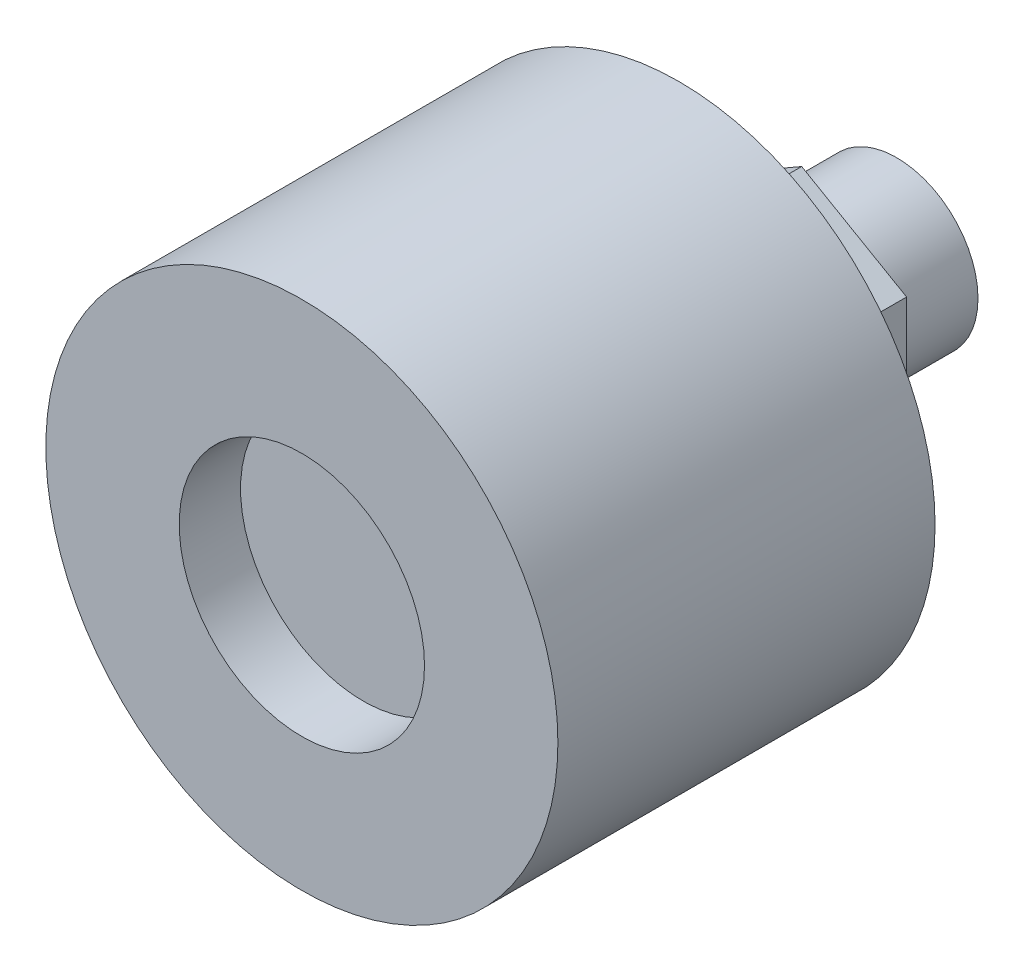
SolidWorks part; units mm, degrees
material "1060 Alloy"
ref_plane "Front Plane" through (0, 0, 0) normal (0, 0, 1) x (1, 0, 0)
ref_plane "Top Plane" through (0, 0, 0) normal (0, 1, 0) x (1, 0, 0)
ref_plane "Right Plane" through (0, 0, 0) normal (1, 0, 0) x (0, 0, -1)
sketch "Sketch3" plane through (0, 0, 0) normal (0, 0, 1) x (1, 0, 0)
  circle A0 centre (0, 0) radius 8.35
  circle A1 centre (0, 0) radius 4
  dimension "D1" = 16.7
extrude "Boss-Extrude1" add sketch "Sketch3" along normal blind 1 and the other way blind 1
sketch "Sketch4" plane through (0, 0, -1) normal (0, 0, -1) x (-1, 0, 0)
  circle A0 centre (0, 0) radius 8.35
extrude "Boss-Extrude2" add sketch "Sketch4" along normal blind 10.3
sketch "Sketch5" plane through (0, 0, -11.3) normal (0, 0, -1) x (-1, 0, 0)
  line L0 (0, -3.95) -> (0, 3.95) construction
  line L2 (0, 3.95) -> (-3.4208, 1.975)
  line L3 (-3.4208, 1.975) -> (-3.4208, -1.975)
  line L4 (-3.4208, -1.975) -> (0, -3.95)
  line L5 (0, -3.95) -> (3.4208, -1.975)
  line L6 (3.4208, -1.975) -> (3.4208, 1.975)
  line L7 (3.4208, 1.975) -> (0, 3.95)
  circle A1 centre (0, 0) radius 3.4208 construction
  point P6 (0, 0)
  point P9 (0, 3.95)
  point P13 (0, -3.95)
  dimension "D1" = 7.9
extrude "Boss-Extrude4" add sketch "Sketch5" along normal blind 4
sketch "Sketch6" plane through (0, 0, -15.3) normal (0, 0, -1) x (-1, 0, 0)
  circle A0 centre (0, 0) radius 2.65
  dimension "D1" = 5.3
extrude "Boss-Extrude5" add sketch "Sketch6" along normal blind 3.1
sketch "Sketch7" plane through (0, 0, -18.4) normal (0, 0, -1) x (-1, 0, 0)
  circle A0 centre (0, 0) radius 0.2443
extrude "Cut-Extrude1" cut sketch "Sketch7" against normal blind 2
